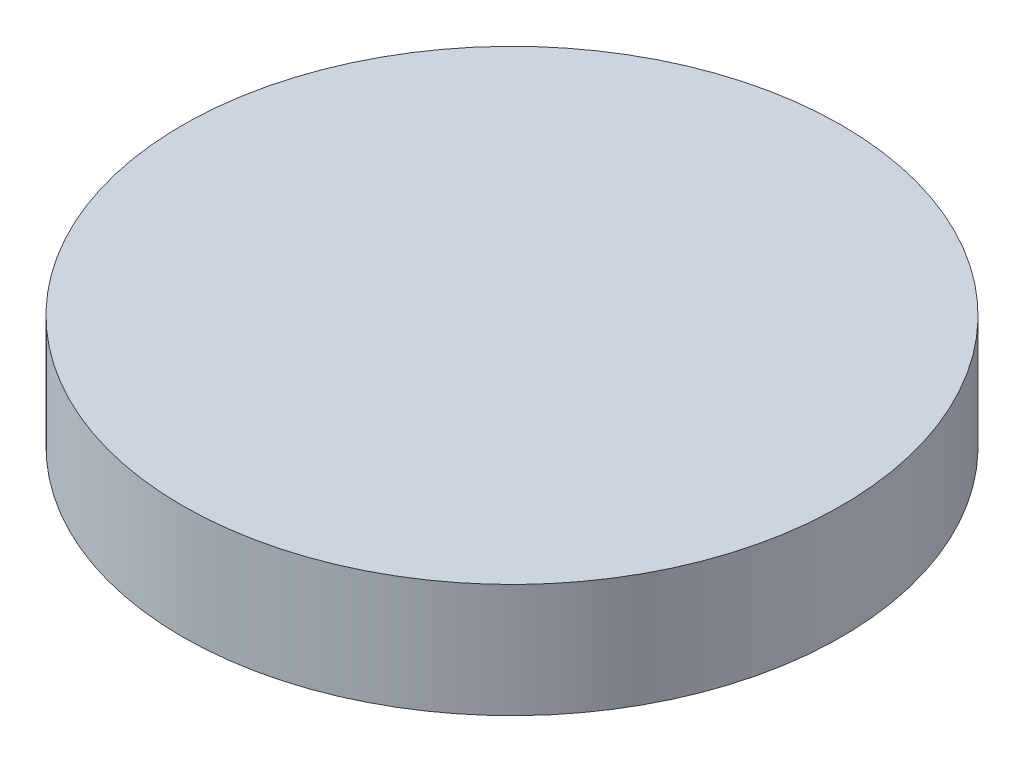
SolidWorks part; units mm, degrees
note: '?' marks a value the reader was unsure of.
ref_plane "Front Plane" through (0, 0, 0) normal (0, 0, 1) x (1, 0, 0)
ref_plane "Top Plane" through (0, 0, 0) normal (0, 1, 0) x (1, 0, 0)
ref_plane "Right Plane" through (0, 0, 0) normal (1, 0, 0) x (0, 0, -1)
sketch "Sketch1" plane through (0, 0, 0) normal (0, 1, 0) x (1, 0, 0)
  circle A0 centre (0, 0) radius 36.83
  dimension "D1" = 73.66
extrude "Boss-Extrude1" add sketch "Sketch1" along normal blind 12.7
ref_axis "Axis1" through (0, -1.27, 0) along (0, 1, 0)?
